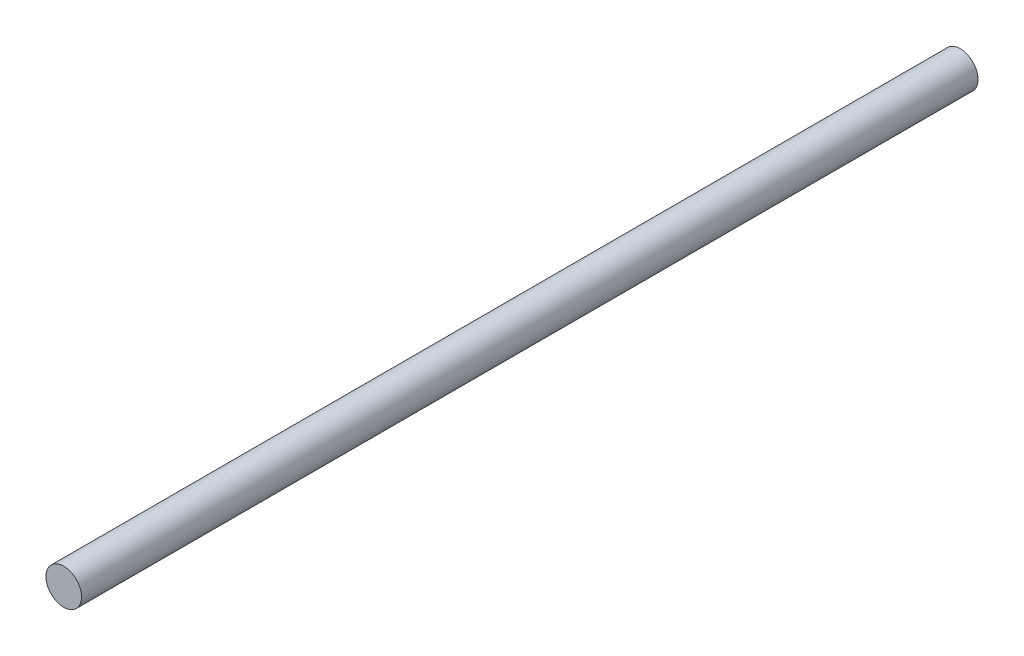
SolidWorks part; units mm, degrees
ref_plane "Front Plane" through (0, 0, 0) normal (0, 0, 1) x (1, 0, 0)
ref_plane "Top Plane" through (0, 0, 0) normal (0, 1, 0) x (1, 0, 0)
ref_plane "Right Plane" through (0, 0, 0) normal (1, 0, 0) x (0, 0, -1)
sketch "Sketch1" plane through (0, 0, 0) normal (0, 0, 1) x (1, 0, 0)
  circle A0 centre (0, 0) radius 2.3813
  dimension "D1" = 4.7625
extrude "Boss-Extrude1" add sketch "Sketch1" along normal blind 120
